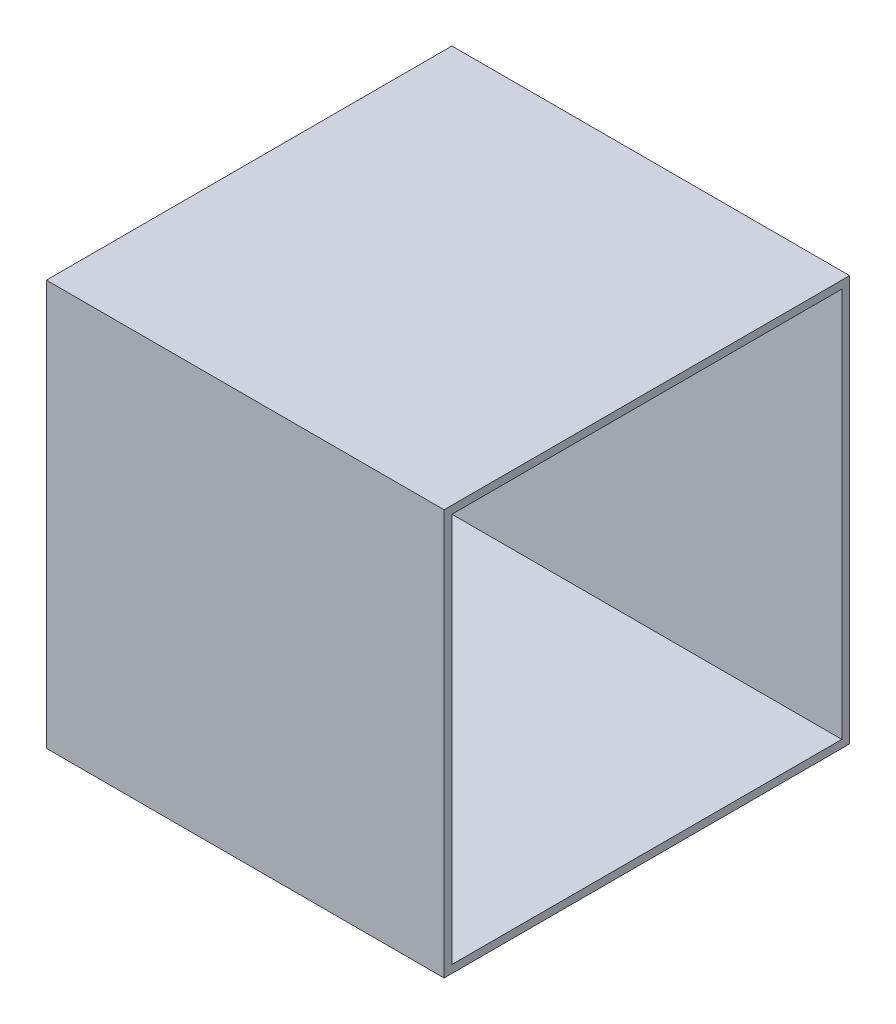
SolidWorks part; units mm, degrees
ref_plane "Front Plane" through (0, 0, 0) normal (0, 0, 1) x (1, 0, 0)
ref_plane "Top Plane" through (0, 0, 0) normal (0, 1, 0) x (1, 0, 0)
ref_plane "Right Plane" through (0, 0, 0) normal (1, 0, 0) x (0, 0, -1)
sketch "Sketch1" plane through (0, 0, 0) normal (0, 0, 1) x (1, 0, 0)
  line L0 (3.6892, -1.2554) -> (3.6892, -2.2554)
  line L1 (-1.2944, 1.2446) -> (3.6892, 1.2446)
  line L2 (-1.2944, 1.2446) -> (-1.2944, -1.2554)
  line L3 (-1.2944, -1.2554) -> (3.6892, -1.2554)
  line L4 (3.6892, 1.2446) -> (3.6892, -1.2554)
  line L5 (-1.2944, 1.2446) -> (3.6892, -1.2554) construction
  line L6 (-1.2944, -1.2554) -> (3.6892, 1.2446) construction
  line L7 (3.6892, -2.2554) -> (-1.2944, -2.2554)
  line L8 (-1.2944, -2.2554) -> (-1.2944, -1.2554)
  line L9 (3.6892, 1.2446) -> (3.6892, 2.2446)
  line L10 (3.6892, 2.2446) -> (-1.2944, 2.2446)
  line L11 (-1.2944, 2.2446) -> (-1.2944, 1.2446)
  circle A0 centre (-0.1026, -0.0054) radius 0.3
  circle A1 centre (1.1974, -0.0054) radius 0.3
  circle A2 centre (2.4974, -0.0054) radius 0.3
  dimension "D1" = 3
  dimension "D3" = 0.6
  dimension "D4" = 1.3
  dimension "D2" = 2.5
  dimension "D5" = 1
  dimension "D6" = 1
extrude "Boss-Extrude1" add sketch "Sketch1" along normal blind 2 contours L4 L1 L2 L3 A2 A1 A0 | L8 L7 L0 L3 | L10 L11 L1 L9 region at (1.1974, -1.7554, 0) region at (1.1974, -1.1996, 0) region at (1.1974, 1.7446, 0)
ref_plane "Plane1" through (0, 0, -0.5) normal (0, 0, -1) x (-1, 0, 0)
extrude "Boss-Extrude4" add sketch "Sketch1<4>" against normal blind 0.5 contours L10 L11 L1 L9 | L8 L7 L0 L3 region at (1.1974, -1.7554, 0) region at (1.1974, 1.7446, 0)
sketch "Sketch1<4>" plane through (0, 0, 0) normal (0, 0, 1) x (1, 0, 0) same geometry as "Sketch1"
mirror "Mirror1" about plane through (0, 0, -0.5) normal (0, 0, -1) of bodies 106 101
sketch "Sketch2" plane through (-1.2944, 0, 0) normal (-1, 0, 0) x (0, 0, 1)
  line L0 (-1, -0.0054) -> (0, -0.0054) construction
  line L2 (-0.5, -0.0054) -> (-20.5, -0.0054) construction
  line L3 (-20.5, -20.0054) -> (29.5, -20.0054)
  line L4 (-20.5, -20.0054) -> (-20.5, 29.9946)
  line L5 (-20.5, 29.9946) -> (29.5, 29.9946)
  line L6 (29.5, -20.0054) -> (29.5, 29.9946)
  line L7 (-0.5, -0.0054) -> (-0.5, -20.0054) construction
  line L8 (-1, 1.2446) -> (-1, -1.2554) construction
  line L9 (0, 1.2446) -> (0, -1.2554) construction
  dimension "D1" = 50
  dimension "D2" = 50
  dimension "D3" = 20
  dimension "D4" = 20
extrude "Boss-Extrude2" add sketch "Sketch2" along normal blind 1
extrude "Extrude-Thin1" add sketch "Sketch2<2>" against normal blind 50 and the other way blind 1 separate body thin thin type one direction wall 1
sketch "Sketch2<2>" plane through (-1.2944, 0, 0) normal (-1, 0, 0) x (0, 0, 1) same geometry as "Sketch2"
